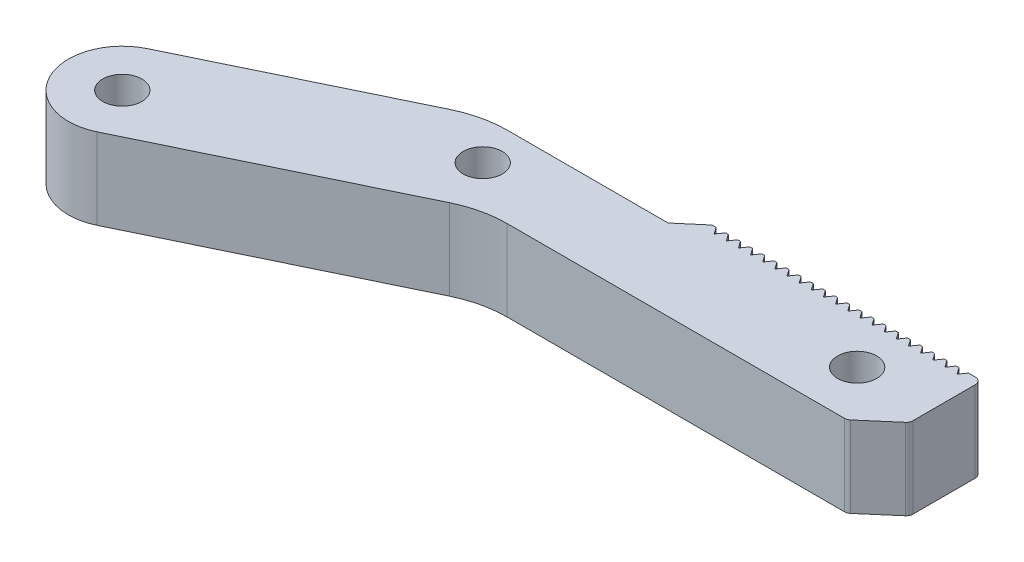
SolidWorks part; units mm, degrees
material "Aleación 6061"
ref_plane "Alzado" through (0, 0, 0) normal (0, 0, 1) x (1, 0, 0)
ref_plane "Planta" through (0, 0, 0) normal (0, 1, 0) x (1, 0, 0)
ref_plane "Vista lateral" through (0, 0, 0) normal (1, 0, 0) x (0, 0, -1)
sketch "Croquis1" plane through (0, 0, 0) normal (0, 1, 0) x (1, 0, 0)
  line L83 (5.4912, -22.6523) -> (27.2532, -22.6523) construction
  line L84 (25.9032, -21.6523) -> (25.0032, -21.6523) construction
  line L85 (7.2532, -21.1523) -> (7.2532, -22.6523) construction
  line L86 (27.2532, -21.1523) -> (7.2532, -21.1523) construction
  line L87 (-5.2468, -25.6523) -> (-23.2532, -25.6523) construction
  line L88 (-5.2468, -25.6523) -> (-23.2532, -34.3569) construction
  line L89 (27.2532, -25.6523) -> (-5.2468, -25.6523) construction
  line L90 (24.7532, -28.6523) -> (27.2532, -26.5023)
  line L91 (27.2532, -21.1523) -> (27.2532, -22.6523)
  line L92 (7.2532, -21.1523) -> (5.4912, -22.6523)
  line L93 (7.3532, -21.1523) -> (7.2532, -21.1523)
  line L94 (8.2532, -21.1523) -> (7.9032, -21.6523)
  line L95 (7.5532, -21.1523) -> (7.3532, -21.1523)
  line L96 (7.9032, -21.6523) -> (7.5532, -21.1523)
  line L97 (9.1532, -21.1523) -> (8.8032, -21.6523)
  line L98 (8.4532, -21.1523) -> (8.2532, -21.1523)
  line L99 (8.8032, -21.6523) -> (8.4532, -21.1523)
  line L100 (10.0532, -21.1523) -> (9.7032, -21.6523)
  line L101 (9.3532, -21.1523) -> (9.1532, -21.1523)
  line L102 (9.7032, -21.6523) -> (9.3532, -21.1523)
  line L103 (10.9532, -21.1523) -> (10.6032, -21.6523)
  line L104 (10.2532, -21.1523) -> (10.0532, -21.1523)
  line L105 (10.6032, -21.6523) -> (10.2532, -21.1523)
  line L106 (11.8532, -21.1523) -> (11.5032, -21.6523)
  line L107 (11.1532, -21.1523) -> (10.9532, -21.1523)
  line L108 (11.5032, -21.6523) -> (11.1532, -21.1523)
  line L109 (12.7532, -21.1523) -> (12.4032, -21.6523)
  line L110 (12.0532, -21.1523) -> (11.8532, -21.1523)
  line L111 (12.4032, -21.6523) -> (12.0532, -21.1523)
  line L112 (13.6532, -21.1523) -> (13.3032, -21.6523)
  line L113 (12.9532, -21.1523) -> (12.7532, -21.1523)
  line L114 (13.3032, -21.6523) -> (12.9532, -21.1523)
  line L115 (14.5532, -21.1523) -> (14.2032, -21.6523)
  line L116 (13.8532, -21.1523) -> (13.6532, -21.1523)
  line L117 (14.2032, -21.6523) -> (13.8532, -21.1523)
  line L118 (15.4532, -21.1523) -> (15.1032, -21.6523)
  line L119 (14.7532, -21.1523) -> (14.5532, -21.1523)
  line L120 (15.1032, -21.6523) -> (14.7532, -21.1523)
  line L121 (16.3532, -21.1523) -> (16.0032, -21.6523)
  line L122 (15.6532, -21.1523) -> (15.4532, -21.1523)
  line L123 (16.0032, -21.6523) -> (15.6532, -21.1523)
  line L124 (17.2532, -21.1523) -> (16.9032, -21.6523)
  line L125 (16.5532, -21.1523) -> (16.3532, -21.1523)
  line L126 (16.9032, -21.6523) -> (16.5532, -21.1523)
  line L127 (18.1532, -21.1523) -> (17.8032, -21.6523)
  line L128 (17.4532, -21.1523) -> (17.2532, -21.1523)
  line L129 (17.8032, -21.6523) -> (17.4532, -21.1523)
  line L130 (19.0532, -21.1523) -> (18.7032, -21.6523)
  line L131 (18.3532, -21.1523) -> (18.1532, -21.1523)
  line L132 (18.7032, -21.6523) -> (18.3532, -21.1523)
  line L133 (19.9532, -21.1523) -> (19.6032, -21.6523)
  line L134 (19.2532, -21.1523) -> (19.0532, -21.1523)
  line L135 (19.6032, -21.6523) -> (19.2532, -21.1523)
  line L136 (20.8532, -21.1523) -> (20.5032, -21.6523)
  line L137 (20.1532, -21.1523) -> (19.9532, -21.1523)
  line L138 (20.5032, -21.6523) -> (20.1532, -21.1523)
  line L139 (21.7532, -21.1523) -> (21.4032, -21.6523)
  line L140 (21.0532, -21.1523) -> (20.8532, -21.1523)
  line L141 (21.4032, -21.6523) -> (21.0532, -21.1523)
  line L142 (22.6532, -21.1523) -> (22.3032, -21.6523)
  line L143 (21.9532, -21.1523) -> (21.7532, -21.1523)
  line L144 (22.3032, -21.6523) -> (21.9532, -21.1523)
  line L145 (23.5532, -21.1523) -> (23.2032, -21.6523)
  line L146 (22.8532, -21.1523) -> (22.6532, -21.1523)
  line L147 (23.2032, -21.6523) -> (22.8532, -21.1523)
  line L148 (24.4532, -21.1523) -> (24.1032, -21.6523)
  line L149 (23.7532, -21.1523) -> (23.5532, -21.1523)
  line L150 (24.1032, -21.6523) -> (23.7532, -21.1523)
  line L151 (25.3532, -21.1523) -> (25.0032, -21.6523)
  line L152 (24.6532, -21.1523) -> (24.4532, -21.1523)
  line L153 (25.0032, -21.6523) -> (24.6532, -21.1523)
  line L154 (25.5532, -21.1523) -> (25.3532, -21.1523)
  line L155 (26.2532, -21.1523) -> (27.2532, -21.1523)
  line L156 (25.9032, -21.6523) -> (25.5532, -21.1523)
  line L157 (26.2532, -21.1523) -> (25.9032, -21.6523)
  line L158 (27.2532, -22.6523) -> (27.2532, -21.1523)
  line L159 (-5.2468, -22.6523) -> (-8.2315, -22.6523)
  line L160 (-24.9941, -30.7557) -> (-8.2315, -22.6523)
  line L161 (-21.5123, -37.9582) -> (-2.2621, -28.6523)
  line L162 (24.7532, -28.6523) -> (-2.2621, -28.6523)
  line L163 (27.2532, -22.6523) -> (27.2532, -26.5023)
  line L164 (5.4912, -22.6523) -> (-5.2468, -22.6523)
  circle A4 centre (21.7532, -24.9023) radius 1.45
  circle A5 centre (-5.2468, -25.6523) radius 1.45
  circle A6 centre (-23.2532, -34.3569) radius 1.45
  arc A7 (-21.5123, -37.9582) -> (-24.9941, -30.7557) centre (-23.2532, -34.3569) cw
  point P173 (10.9968, -25.6523)
extrude "Saliente-Extruir1" add sketch "Croquis1" along normal blind 6 contours A7 L161 L162 L90 L163 L91 L155 L157 L156 L154 L151 L153 L152 L148 L150 L149 L145 L147 L146 L142 L144 L143 L139 L141 L140 L136 L138 L137 L133 L135 L134 L130 L132 L131 L127 L129 L128 L124 L126 L125 L121 L123 L122 L118 L120 L119 L115 L117 L116 L112 L114 region at (-0.8294, 0, 27.6459)
fillet "Redondeo1" radius 0.5 3 edges at (24.7532, 3, 28.6523) (27.2532, 3, 26.5023) (27.2532, 3, 21.1523)
fillet "Redondeo2" radius 8 2 edges at (-2.2621, 3, 28.6523) (-8.2315, 3, 22.6523)
ref_point "rfinger_cf_center"
ref_plane "rfinger_rotation_plain" through (0, 0, 34.3569) normal (0, 0, -1) x (-1, 0, 0)
ref_axis "rfinger_rotation_axis" through (-23.2532, -1.7531, 34.3569) along (0, 1, 0)
